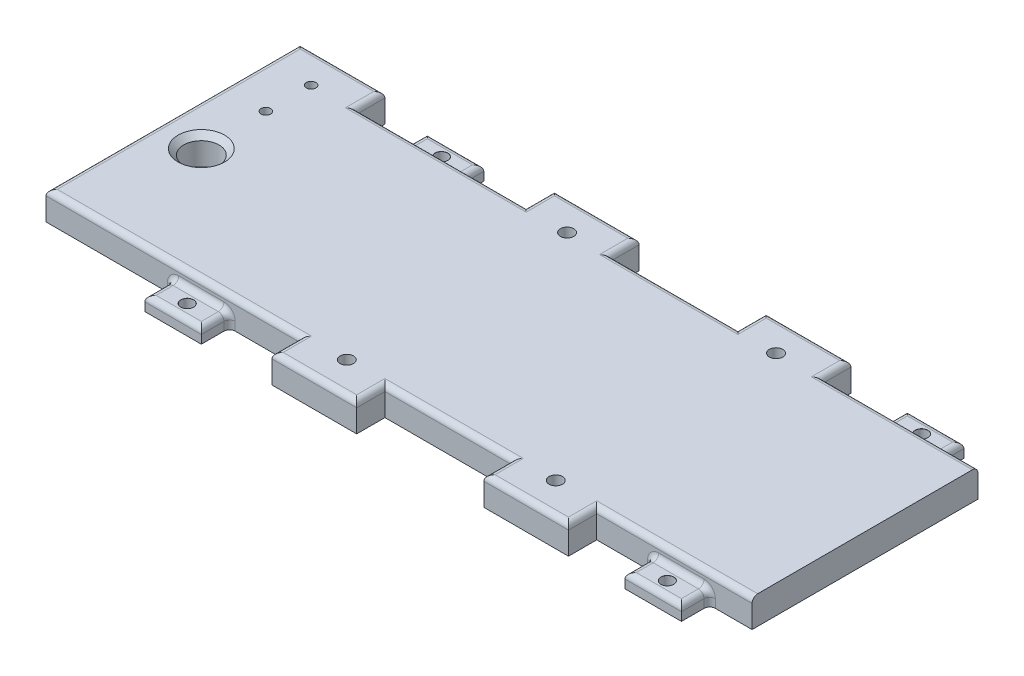
SolidWorks part; units mm, degrees
ref_plane "Front Plane" through (0, 0, 0) normal (0, 0, 1) x (1, 0, 0)
ref_plane "Top Plane" through (0, 0, 0) normal (0, 1, 0) x (1, 0, 0)
ref_plane "Right Plane" through (0, 0, 0) normal (1, 0, 0) x (0, 0, -1)
sketch "Sketch1" plane through (0, 0, 0) normal (0, 1, 0) x (1, 0, 0)
  line L1 (130, -50) -> (-130, -50)
  line L2 (130, -50) -> (130, 50)
  line L3 (130, 50) -> (-130, 50)
  line L4 (-130, -50) -> (-130, 50)
  line L5 (0, 50) -> (0, -50) construction
  line L6 (130, 0) -> (-130, 0) construction
  point P0 (0, 0)
  dimension "D1" = 260
  dimension "D2" = 100
extrude "Boss-Extrude1" add sketch "Sketch1" along normal blind 10
sketch "Sketch3" plane through (0, 10, 0) normal (0, 1, 0) x (1, 0, 0)
  line L0 (130, 50) -> (-130, 50) construction
  line L1 (130, 50) -> (75, 50)
  line L2 (130, 50) -> (130, 40)
  line L3 (130, 40) -> (75, 40)
  line L4 (75, 50) -> (75, 40)
  line L5 (130, -50) -> (75, -50)
  line L6 (130, -50) -> (130, -40)
  line L7 (130, -40) -> (75, -40)
  line L8 (75, -50) -> (75, -40)
  line L9 (-130, -50) -> (-30, -50)
  line L10 (-130, -50) -> (-130, -40)
  line L11 (-120, -40) -> (-30, -40)
  line L12 (-30, -50) -> (-30, -40)
  line L13 (-90, 50) -> (-30, 50)
  line L14 (-90, 50) -> (-90, 40)
  line L15 (-90, 40) -> (-30, 40)
  line L16 (-30, 50) -> (-30, 40)
  line L17 (-130, 50) -> (-130, -50) construction
  line L18 (-130, -50) -> (130, -50) construction
  line L19 (0, 50) -> (45, 50)
  line L20 (0, 50) -> (0, 40)
  line L21 (0, 40) -> (45, 40)
  line L22 (45, 50) -> (45, 40)
  line L23 (0, -50) -> (45, -50)
  line L24 (0, -50) -> (0, -40)
  line L25 (0, -40) -> (45, -40)
  line L26 (45, -50) -> (45, -40)
  line L28 (-130, 50) -> (-120, 50)
  line L29 (-130, 50) -> (-130, -40)
  line L31 (-120, 50) -> (-120, -40)
  dimension "D1" = 10
  dimension "D2" = 55
  dimension "D3" = 55
  dimension "D4" = 10
  dimension "D5" = 10
  dimension "D6" = 100
  dimension "D7" = 10
  dimension "D8" = 60
  dimension "D9" = 40
  dimension "D10" = 10
  dimension "D11" = 45
  dimension "D12" = 30
  dimension "D13" = 10
  dimension "D14" = 45
  dimension "D15" = 10
extrude "Cut-Extrude2" cut sketch "Sketch3" against normal through all
sketch "Sketch4" plane through (0, 10, 0) normal (0, 1, 0) x (1, 0, 0)
  circle A0 centre (59.5, 39) radius 2.375
  circle A1 centre (-14.5, 39) radius 2.375
  circle A2 centre (59.5, -39) radius 2.375
  circle A3 centre (-14.5, -39) radius 2.375
  dimension "D1" = 4.75
  dimension "D2" = 4.75
  dimension "D3" = 4.75
  dimension "D4" = 4.75
sketch "Sketch5" plane through (0, 0, 0) normal (0, -1, 0) x (1, 0, 0)
  line L0 (-30, 40) -> (-120, 40) construction
  line L1 (-75, 40) -> (-55, 40)
  line L2 (-75, 40) -> (-75, 50)
  line L3 (-75, 50) -> (-55, 50)
  line L4 (-55, 40) -> (-55, 50)
  line L5 (-90, -40) -> (-30, -40) construction
  line L6 (-75, -40) -> (-55, -40)
  line L7 (-75, -40) -> (-75, -50)
  line L8 (-75, -50) -> (-55, -50)
  line L9 (-55, -40) -> (-55, -50)
  line L10 (130, 40) -> (75, 40) construction
  line L11 (95, 40) -> (115, 40)
  line L12 (95, 40) -> (95, 50)
  line L13 (95, 50) -> (115, 50)
  line L14 (115, 40) -> (115, 50)
  line L15 (75, -40) -> (130, -40) construction
  line L16 (95, -40) -> (115, -40)
  line L17 (95, -40) -> (95, -50)
  line L18 (95, -50) -> (115, -50)
  line L19 (115, -40) -> (115, -50)
  line L20 (130, 40) -> (130, -40) construction
  dimension "D1" = 20
  dimension "D2" = 20
  dimension "D3" = 20
  dimension "D4" = 20
  dimension "D5" = 10
  dimension "D6" = 10
  dimension "D7" = 10
  dimension "D8" = 10
  dimension "D9" = 150
  dimension "D10" = 15
extrude "Boss-Extrude2" add sketch "Sketch5" against normal blind 5
fillet "Fillet1" radius 2 45 edges at (-60, 10, -40) (-30, 10, -45) (-15, 10, -50) (60, 10, -50) (75, 10, -45) (102.5, 10, -40) (102.5, 10, 40) (75, 10, 45) (-30, 10, 45) (-75, 10, 40) (-90, 10, -45) (60, 10, 50) (45, 10, 45) (22.5, 10, 40) (0, 10, 45) (-15, 10, 50) (0, 10, -45) (22.5, 10, -40) (45, 10, -45) (-120, 10, -5) (-105, 10, -50) (-75, 2.5, 40) (-55, 2.5, 40) (95, 2.5, 40) (115, 2.5, 40) (115, 2.5, -40) (95, 2.5, -40) (-55, 2.5, -40) (-75, 2.5, -40) (-65, 5, 40) (-55, 5, 45) (-65, 5, 50) (-75, 5, 45) (105, 5, 40) (115, 5, 45) (105, 5, 50) (95, 5, 45) (105, 5, -50) (115, 5, -45) (105, 5, -40) (95, 5, -45) (-65, 5, -50) (-55, 5, -45) (-65, 5, -40) (-75, 5, -45)
sketch "Sketch2" plane through (0, 10, 0) normal (0, 1, 0) x (1, 0, 0)
  line L1 (-120, -40) -> (-120, 50) construction
  circle A0 centre (-105, 0) radius 6.25
  dimension "D2" = 12.5
  dimension "D1" = 15
extrude "Cut-Extrude1" cut sketch "Sketch2" against normal through all
chamfer "Chamfer1" distance 2 angle 45 1 edges at (-105, 10, 6.25)
extrude "Cut-Extrude3" cut sketch "Sketch4" against normal blind 6.2
sketch "Sketch9" plane through (0, 5, 0) normal (0, 1, 0) x (1, 0, 0)
  point P0 (-65, 45)
  point P2 (105, 45)
  point P4 (105, -45)
  point P6 (-65, -45)
hole_wizard "M4 Clearance Hole1" positions "Sketch9" profile "Sketch7" hole size "M4" standard "ANSI Metric" end condition through all
sketch "Sketch7" plane through (-65, 5, -45) normal (1, 0, 0) x (0, 0, 1)
  line L0 (0, 0) -> (0, 5)
  line L1 (0, 5) -> (2.25, 5)
  line L2 (2.25, 5) -> (2.25, 0.025)
  line L3 (2.25, 0.025) -> (2.275, 0)
  line L5 (2.275, 0) -> (0, 0)
  line L6 (-2.25, 0.025) -> (-2.275, 0) construction
  line L11 (0, -6.35) -> (0, 107.95) construction
  dimension "Thru Hole Dia." = 4.5
  dimension "Thru Hole Depth" = 5
  dimension "Near C'Sink Dia." = 4.55
  dimension "Near C'Sink Angle" = 90
sketch "Sketch12" plane through (0, 0, 0) normal (0, -1, 0) x (-1, 0, 0)
  line L1 (90, 50) -> (120, 50) construction
  line L2 (120, -40) -> (120, 50) construction
  point P0 (105, 38.8589)
  point P2 (105, 22.8589)
  dimension "D1" = 16
  dimension "D2" = 11.1411
  dimension "D3" = 15
hole_wizard "M3 Clearance Hole1" positions "Sketch12" profile "Sketch11" hole size "M3" standard "ANSI Metric" end condition through all
sketch "Sketch11" plane through (-105, 0, -38.8589) normal (1, 0, 0) x (0, 0, -1)
  line L0 (0, 0) -> (0, 10)
  line L1 (0, 10) -> (1.7, 10)
  line L2 (1.7, 10) -> (1.7, 0)
  line L5 (1.7, 0) -> (0, 0)
  line L11 (0, -6.35) -> (0, 107.95) construction
  dimension "Thru Hole Dia." = 3.4
  dimension "Thru Hole Depth" = 10
sketch "Sketch13" plane through (0, 0, 0) normal (0, -1, 0) x (1, 0, 0)
  circle A0 centre (-105, -22.8589) radius 3.5
  circle A1 centre (-105, -38.8589) radius 3.5
  dimension "D1" = 7
  dimension "D2" = 7
extrude "Cut-Extrude4" cut sketch "Sketch13" against normal blind 5
